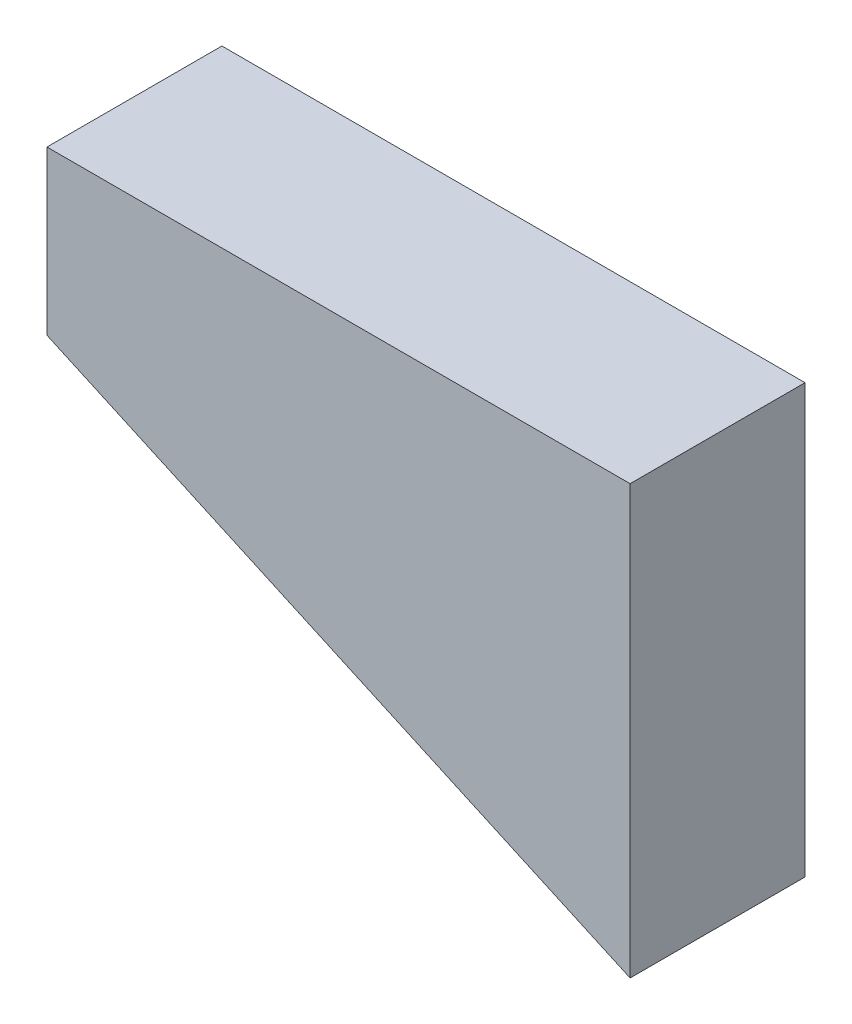
SolidWorks part; units mm, degrees
ref_plane "Front Plane" through (0, 0, 0) normal (0, 0, 1) x (1, 0, 0)
ref_plane "Top Plane" through (0, 0, 0) normal (0, 1, 0) x (1, 0, 0)
ref_plane "Right Plane" through (0, 0, 0) normal (1, 0, 0) x (0, 0, -1)
sketch "Sketch1" plane through (0, 0, 0) normal (0, 0, 1) x (1, 0, 0)
  line L33 (-673.6845, 1780.4468) -> (-737.1845, 1780.4468)
  line L35 (-737.1845, 1762.6932) -> (-673.6845, 1733.8295)
  line L63 (-737.1845, 1780.4468) -> (-737.1845, 1762.6932)
  line L67 (-673.6845, 1780.4468) -> (-673.6845, 1733.8295)
  line L68 (-673.6845, 1780.4468) -> (-673.6845, 1762.6932) construction
extrude "Boss-Extrude1" add sketch "Sketch1" along normal blind 19.05 contours L67 L33 L63 L35 region at (-700.689, 1763.2755, 0)
